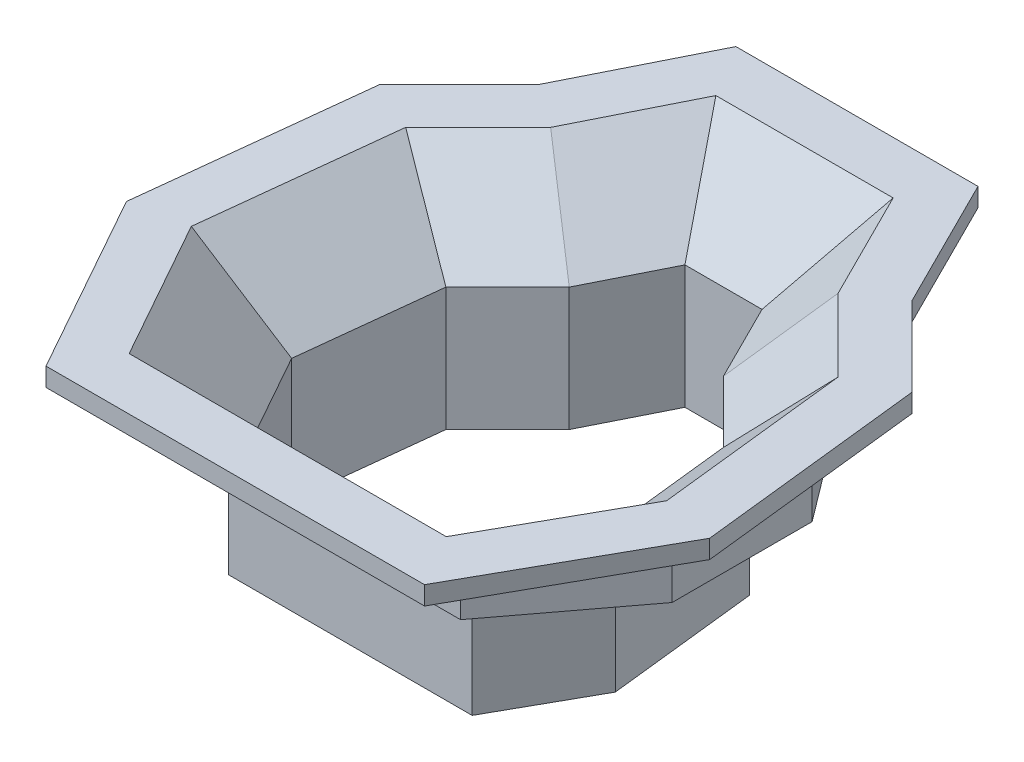
SolidWorks part; units mm, degrees
note: The reader was unsure of these and kept them because the rebuilt part matched: shared geometry of "Sketch3<4>".
ref_plane "Front Plane" through (0, 0, 0) normal (0, 0, 1) x (1, 0, 0)
ref_plane "Top Plane" through (0, 0, 0) normal (0, 1, 0) x (1, 0, 0)
ref_plane "Right Plane" through (0, 0, 0) normal (1, 0, 0) x (0, 0, -1)
sketch "Sketch2" plane through (0, 0, 0) normal (0, 0, 1) x (1, 0, 0)
  line L0 (0, 0) -> (0, 0.5)
  line L2 (0, 0.5) -> (0, 3.1276)
  dimension "D1" = 2.6276
  dimension "D2" = 0.5
ref_plane "Plane1" through (0, 0.5, 0) normal (0, 1, 0) x (1, 0, 0)
sketch "Sketch3" plane through (0, 0.5, 0) normal (0, 1, 0) x (1, 0, 0)
  line L1 (-4.5, 7) -> (-5, 2.5)
  line L2 (-5, 2.5) -> (-3.6, 0)
  line L3 (-3.6, 0) -> (3.6, 0)
  line L4 (3.6, 0) -> (5, 2.5)
  line L5 (5, 2.5) -> (4.5, 7)
  line L7 (1.25, 11.5) -> (-1.25, 11.5)
  line L8 (-5, 2.5) -> (5, 2.5) construction
  line L9 (0, 11.5) -> (0, 0) construction
  line L10 (-4.5, 7) -> (4.5, 7) construction
  line L19 (-2.5, 9) -> (2.5, 9) construction
  line L20 (5.6176, 2.3749) -> (5.0731, 7.2754)
  line L21 (2.9931, 9.3554) -> (5.0731, 7.2754)
  line L22 (1.6208, 12.1) -> (2.9931, 9.3554)
  line L23 (1.6208, 12.1) -> (-1.6208, 12.1)
  line L24 (-4.5, 7) -> (-2.5, 9)
  line L25 (-2.5, 9) -> (-1.25, 11.5)
  line L26 (1.25, 11.5) -> (2.5, 9)
  line L27 (2.5, 9) -> (4.5, 7)
  line L32 (-2.9931, 9.3554) -> (-1.6208, 12.1)
  line L33 (-5.0731, 7.2754) -> (-2.9931, 9.3554)
  line L34 (-5.0731, 7.2754) -> (-5.6176, 2.3749)
  line L35 (-5.6176, 2.3749) -> (-3.9517, -0.6)
  line L36 (-3.9517, -0.6) -> (3.9517, -0.6)
  line L37 (3.9517, -0.6) -> (5.6176, 2.3749)
  point P6 (0, 9)
  point P19 (0, 7)
  point P23 (0, 2.5)
  dimension "D1" = 10
  dimension "D2" = 11.5
  dimension "D3" = 2.5
  dimension "D4" = 7
  dimension "D5" = 9
  dimension "D6" = 2.5
  dimension "D7" = 7.2
  dimension "D9" = 5
  dimension "D10" = 2
  dimension "D8" = 0.6
sketch "Sketch4" plane through (0, 0, 0) normal (1, 0, 0) x (0, 0, -1)
  line L0 (0, 0.5) -> (-0.6, 0.5)
  line L1 (0, 0.5) -> (-2.6276, 3.1276)
  line L3 (0, 0.5) -> (0, 3.1276) construction
  line L4 (-2.6276, 3.1276) -> (-2.6276, 2.5276) construction
  line L5 (-2.6276, 2.5276) -> (-0.6, 0.5)
  line L12 (-1.2151, 3.1276) -> (2.6254, 3.1276) construction
  line L13 (-2.6276, 2.5276) -> (-4.3276, 2.5276)
  line L14 (-4.3276, 2.5276) -> (-4.3276, 3.1276)
  line L15 (-4.3276, 3.1276) -> (-2.6276, 3.1276)
  dimension "D1" = 0.6
  dimension "D2" = 1.7
  dimension "D3" = 2.6276
extrude "Boss-Extrude3" add sketch "Sketch3<4>" against normal blind 4
sketch "Sketch3<4>" plane through (0, 0.5, 0) normal (0, 1, 0) x (1, 0, 0) same geometry as "Sketch3"
sketch "Sketch57" plane through (0, 0.5, 0) normal (0, 1, 0) x (1, 0, 0)
  line L0 (-2.561, 13.6) -> (-8.0229, 6.3518) construction
  line L1 (-8.0229, 6.3518) -> (-8.0229, 1.8118)
  line L2 (-8.0229, 1.8118) -> (-5.0752, -2.1)
  line L3 (2.561, 13.6) -> (8.0229, 6.3518) construction
  line L4 (8.0229, 6.3518) -> (8.0229, 1.8118)
  line L5 (8.0229, 1.8118) -> (5.0752, -2.1)
  line L6 (-2.561, 13.6) -> (2.561, 13.6) construction
  line L8 (0, 13.6) -> (0, -2.1) construction
  line L9 (0, 4.0818) -> (-8.0229, 4.0818) construction
  line L10 (0, 11.5) -> (0, 0) construction
  line L11 (1.6208, 12.1) -> (-1.6208, 12.1) construction
  line L12 (-3.9517, -0.6) -> (3.9517, -0.6) construction
  line L13 (-8.0229, 6.3518) -> (-5.0752, 10.2636)
  line L14 (-5.0752, 10.2636) -> (5.0752, 10.2636)
  line L15 (5.0752, 10.2636) -> (8.0229, 6.3518)
  line L17 (-8.0229, 6.3518) -> (8.0229, 6.3518) construction
  line L18 (-8.0229, 1.8118) -> (8.0229, 1.8118) construction
  line L19 (-5.0752, -2.1) -> (5.0752, -2.1)
  dimension "D1" = 1.8
  dimension "D2" = 4.54
  dimension "D3" = 53
  dimension "D4" = 1.5
  dimension "D5" = 53
  dimension "D6" = 1.8
  dimension "D7" = 1.5
extrude "Boss-Extrude30" add sketch "Sketch57" along normal blind 2.1
sweep "Sweep3" add profiles "Sketch4" path "Sketch3"
sketch "Sketch60" plane through (0, 0, 0) normal (1, 0, 0) x (0, 0, -1)
  line L0 (-4.3276, 3.1276) -> (-2.6276, 3.1276)
  line L1 (-2.6276, 3.1276) -> (0, 0.5)
  line L6 (0, 3.7276) -> (-4.3276, 3.7276)
  line L7 (-4.3276, 3.7276) -> (-4.3276, 3.1276)
  line L8 (-4.3276, 2.5276) -> (-4.3276, 3.1276) construction
  line L10 (0, 0.5) -> (0.4199, 0.0801)
  line L11 (0.4199, 0.0801) -> (0.4199, 3.7276)
  line L12 (0.4199, 3.7276) -> (0, 3.7276)
sketch "Sketch61" plane through (0, 0.5, 0) normal (0, 1, 0) x (1, 0, 0)
  line L0 (1.25, 11.5) -> (2.5, 9) construction
  line L1 (2.5, 9) -> (4.5, 7) construction
  line L2 (5, 2.5) -> (4.5, 7) construction
  line L3 (3.6, 0) -> (5, 2.5) construction
  line L4 (-3.6, 0) -> (3.6, 0) construction
  line L5 (-5, 2.5) -> (-3.6, 0) construction
  line L6 (-4.5, 7) -> (-5, 2.5) construction
  line L7 (-4.5, 7) -> (-2.5, 9) construction
  line L8 (-2.5, 9) -> (-1.25, 11.5) construction
  line L9 (1.25, 11.5) -> (-1.25, 11.5) construction
  line L10 (1.25, 11.5) -> (2.5, 9)
  line L11 (2.5, 9) -> (4.5, 7)
  line L12 (5, 2.5) -> (4.5, 7)
  line L13 (3.6, 0) -> (5, 2.5)
  line L14 (-3.6, 0) -> (3.6, 0)
  line L15 (-5, 2.5) -> (-3.6, 0)
  line L16 (-4.5, 7) -> (-5, 2.5)
  line L17 (-4.5, 7) -> (-2.5, 9)
  line L18 (-2.5, 9) -> (-1.25, 11.5)
  line L19 (1.25, 11.5) -> (-1.25, 11.5)
sweep "Cut-Sweep10" cut profiles "Sketch60" path "Sketch61"
ref_plane "Plane5" through (0.1471, 0, -0.1952) normal (0.6018, 0, -0.7986) x (0, -1, 0)
ref_plane "Plane6" through (-3.7766, 0, -5.0117) normal (-0.6018, 0, -0.7986) x (0, -1, 0)
sketch "Sketch62" plane through (0.1471, 0, -0.1952) normal (0.6018, 0, -0.7986) x (0, -1, 0)
  line L2 (-0.5, 10.23) -> (-1.5138, 9.2162) construction
  line L3 (-1.5138, 9.2162) -> (-2.5276, 10.23) construction
  line L4 (-2.5276, 10.23) -> (-2.5276, 11.23)
  line L5 (-0.9638, 9.7662) -> (-2.0638, 9.7662)
  line L6 (-1.5138, 9.2162) -> (-1.5138, 11.23) construction
  line L7 (-0.9638, 9.7662) -> (-0.5, 10.23)
  line L8 (-2.0638, 9.7662) -> (-2.5276, 10.23)
  line L9 (-2.5276, 6.391) -> (-2.5276, 12.6596) construction
  line L10 (-2.5276, 11.23) -> (-0.5, 11.23)
  line L11 (-0.5, 11.23) -> (-0.5, 10.23)
  line L12 (-0.5, 10.4) -> (-0.5, -10.4) construction
  line L13 (-2.5276, 10.23) -> (-0.5, 10.23) construction
  line L14 (-2.5276, 10.23) -> (-0.5, 10.23) construction
  dimension "D1" = 90
  dimension "D2" = 1.1
  dimension "D3" = 1
extrude "Cut-Extrude23" cut sketch "Sketch62" along normal through all and the other way through all
sketch "Sketch64" plane through (-3.7766, 0, -5.0117) normal (-0.6018, 0, -0.7986) x (0, -1, 0)
  line L0 (-0.5, 5.317) -> (-1.5138, 4.3032) construction
  line L1 (-0.5, 10.4) -> (-0.5, -10.4) construction
  line L2 (-1.5138, 4.3032) -> (-2.5276, 5.317) construction
  line L3 (-2.5276, 5.317) -> (-2.5276, 6.317)
  line L4 (-2.5276, 6.317) -> (-0.5, 6.317)
  line L5 (-0.5, 6.317) -> (-0.5, 5.317)
  line L6 (-1.5138, 4.3032) -> (-1.5138, 6.317) construction
  line L7 (-0.9638, 4.8532) -> (-2.0638, 4.8532)
  line L8 (-2.5276, 5.317) -> (-2.0638, 4.8532)
  line L9 (-0.9638, 4.8532) -> (-0.5, 5.317)
  line L10 (-2.5276, 5.317) -> (-0.5, 5.317) construction
  dimension "D1" = 1
  dimension "D2" = 90
  dimension "D3" = 1.1
extrude "Cut-Extrude24" cut sketch "Sketch64" against normal through all and the other way through all
